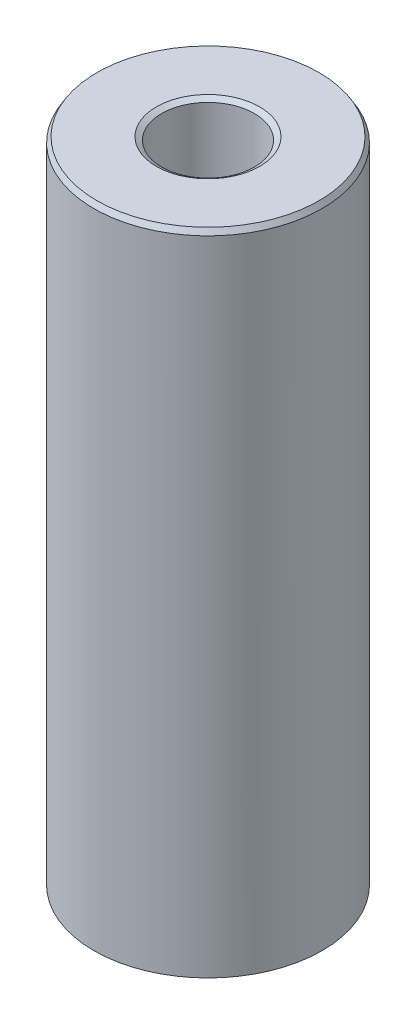
SolidWorks part; units mm, degrees
ref_plane "Front Plane" through (0, 0, 0) normal (0, 0, 1) x (1, 0, 0)
ref_plane "Top Plane" through (0, 0, 0) normal (0, 1, 0) x (1, 0, 0)
ref_plane "Right Plane" through (0, 0, 0) normal (1, 0, 0) x (0, 0, -1)
sketch "Sketch1" plane through (0, 0, 0) normal (0, 1, 0) x (1, 0, 0)
  circle A0 centre (0, 0) radius 52.5
  dimension "SLEEVE_OD" = 105
extrude "Boss-Extrude1" add sketch "Sketch1" along normal blind 299.3764
sketch "Sketch2" plane through (0, 0, 0) normal (0, 1, 0) x (1, 0, 0)
  circle A0 centre (0, 0) radius 21.3353
  dimension "BORE_D" = 42.6707
extrude "Cut-Extrude1" cut sketch "Sketch2" along normal through all
chamfer "Chamfer1" distance 2.4118 angle 30.908 4 edges at (0, 299.3764, 21.3353) (0, 0, 21.3353) (0, 0, 52.5) (0, 299.3764, 52.5) first distance on face at (0, 299.3764, 21.3353) first distance on face at (0, 0, 21.3353) first distance on face at (0, 299.3764, 52.5)
